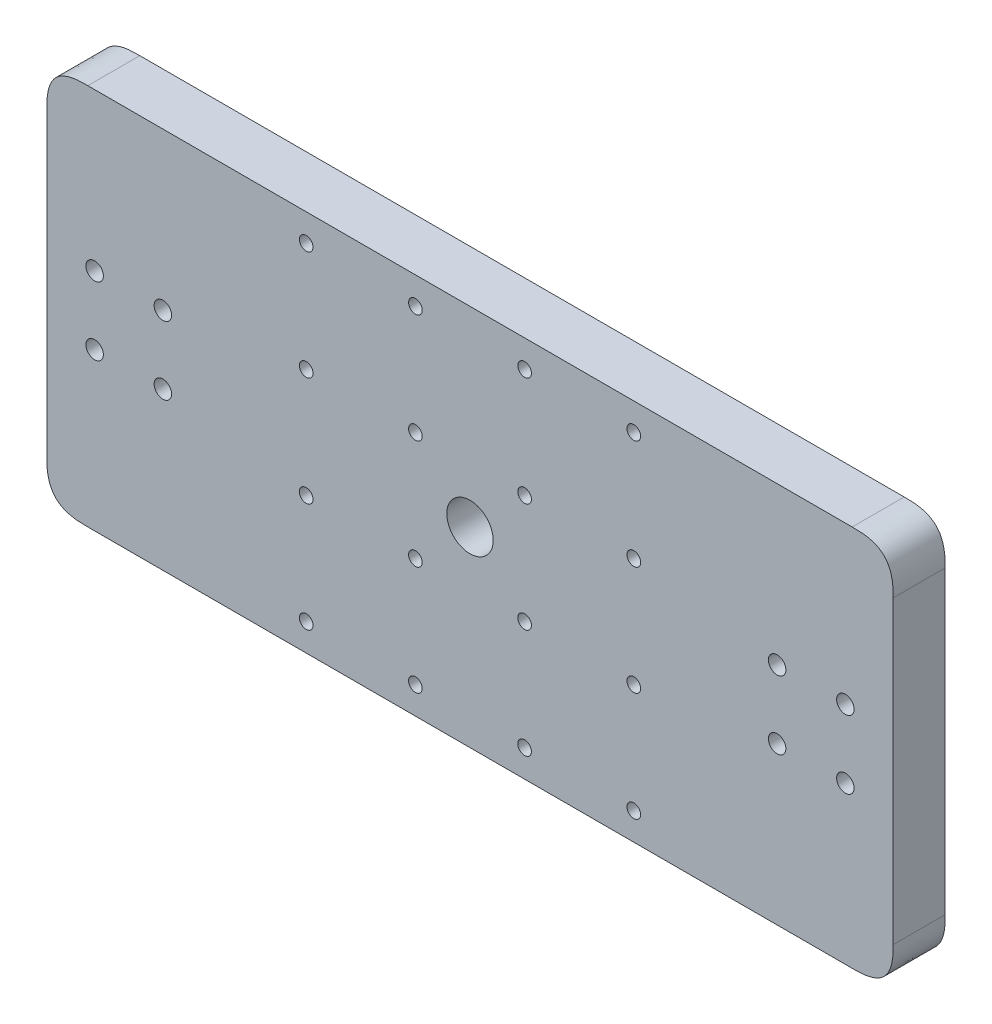
SolidWorks part; units mm, degrees
ref_plane "Front Plane" through (0, 0, 0) normal (0, 0, 1) x (1, 0, 0)
ref_plane "Top Plane" through (0, 0, 0) normal (0, 1, 0) x (1, 0, 0)
ref_plane "Right Plane" through (0, 0, 0) normal (1, 0, 0) x (0, 0, -1)
sketch "Sketch1" plane through (0, 0, 0) normal (0, 0, 1) x (1, 0, 0)
  line L1 (-155, 70) -> (155, 70)
  line L2 (-155, 70) -> (-155, -70)
  line L3 (-155, -70) -> (155, -70)
  line L4 (155, 70) -> (155, -70)
  line L5 (-155, 70) -> (155, -70) construction
  line L6 (-155, -70) -> (155, 70) construction
  point P0 (0, 0)
  dimension "D1" = 310
  dimension "D2" = 140
extrude "Boss-Extrude1" add sketch "Sketch1" along normal blind 19.05
sketch "Sketch5" plane through (0, 0, 19.05) normal (0, 0, 1) x (1, 0, 0)
  line L1 (-60, 60) -> (60, 60) construction
  line L2 (-60, 60) -> (-60, -60) construction
  line L3 (-60, -60) -> (60, -60) construction
  line L4 (60, 60) -> (60, -60) construction
  line L8 (-60, 60) -> (60, -60) construction
  point P0 (-60, 60)
  point P14 (-60, 60)
  dimension "D1" = 120
  dimension "D2" = 120
hole_wizard "Tap Drill for M6x1.0 Tap1" positions "Sketch5" profile "Sketch6" hole size "M6x1.0" standard "ANSI Metric" end condition up to next
sketch "Sketch6" plane through (-60, 60, 19.05) normal (1, 0, 0) x (0, -1, 0)
  line L0 (0, 0) -> (0, 19.05)
  line L1 (0, 19.05) -> (2.5, 19.05)
  line L2 (2.5, 19.05) -> (2.5, 0)
  line L5 (2.5, 0) -> (0, 0)
  line L11 (0, -6.35) -> (0, 107.95) construction
  dimension "Thru Hole Dia." = 5
  dimension "Thru Hole Depth" = 19.05
pattern_linear "LPattern1" count 4 spacing 40 along (1, 0, 0) count 4 spacing 40 along (0, -1, 0) of "Tap Drill for M6x1.0 Tap1"
fillet "Fillet1" radius 15 4 edges at (155, -70, 9.525) (155, 70, 9.525) (-155, 70, 9.525) (-155, -70, 9.525) curvature continuous yes
sketch "Sketch10" plane through (0, 0, 0) normal (0, 0, -1) x (-1, 0, 0)
  point P0 (137.5, -12.5)
  point P3 (137.5, 12.5)
  point P6 (112.5, 12.5)
  point P9 (112.5, -12.5)
  point P12 (-112.5, -12.5)
  point P15 (-137.5, -12.5)
  point P18 (-112.5, 12.5)
  point P21 (-137.5, 12.5)
hole_wizard "M6 Clearance Hole1" positions "Sketch10" profile "Sketch9" hole size "M6" standard "ANSI Metric" end condition through all
sketch "Sketch9" plane through (-137.5, -12.5, 0) normal (1, 0, 0) x (0, 1, 0)
  line L0 (0, 0) -> (0, 19.1)
  line L1 (0, 19.1) -> (3.2, 19.1)
  line L2 (3.2, 19.1) -> (3.2, 0)
  line L5 (3.2, 0) -> (0, 0)
  line L11 (0, -6.35) -> (0, 107.95) construction
  dimension "Thru Hole Dia." = 6.4
  dimension "Thru Hole Depth" = 19.1
sketch "Sketch11" plane through (0, 0, 19.05) normal (0, 0, 1) x (1, 0, 0)
  line L0 (0, 70) -> (0, -70) construction
  line L1 (140, 70) -> (-140, 70) construction
  line L2 (-140, -70) -> (140, -70) construction
  point P6 (0, 0)
sketch "Sketch14" plane through (0, 0, 19.05) normal (0, 0, 1) x (1, 0, 0)
  point P0 (0, 0)
hole_wizard "M16 Clearance Hole1" positions "Sketch14" profile "Sketch13" hole size "M16" standard "ANSI Metric" end condition through all
sketch "Sketch13" plane through (0, 0, 19.05) normal (1, 0, 0) x (0, -1, 0)
  line L0 (0, 0) -> (0, 19.1)
  line L1 (0, 19.1) -> (8.5, 19.1)
  line L2 (8.5, 19.1) -> (8.5, 0)
  line L5 (8.5, 0) -> (0, 0)
  line L11 (0, -6.35) -> (0, 107.95) construction
  dimension "Thru Hole Dia." = 17
  dimension "Thru Hole Depth" = 19.1
